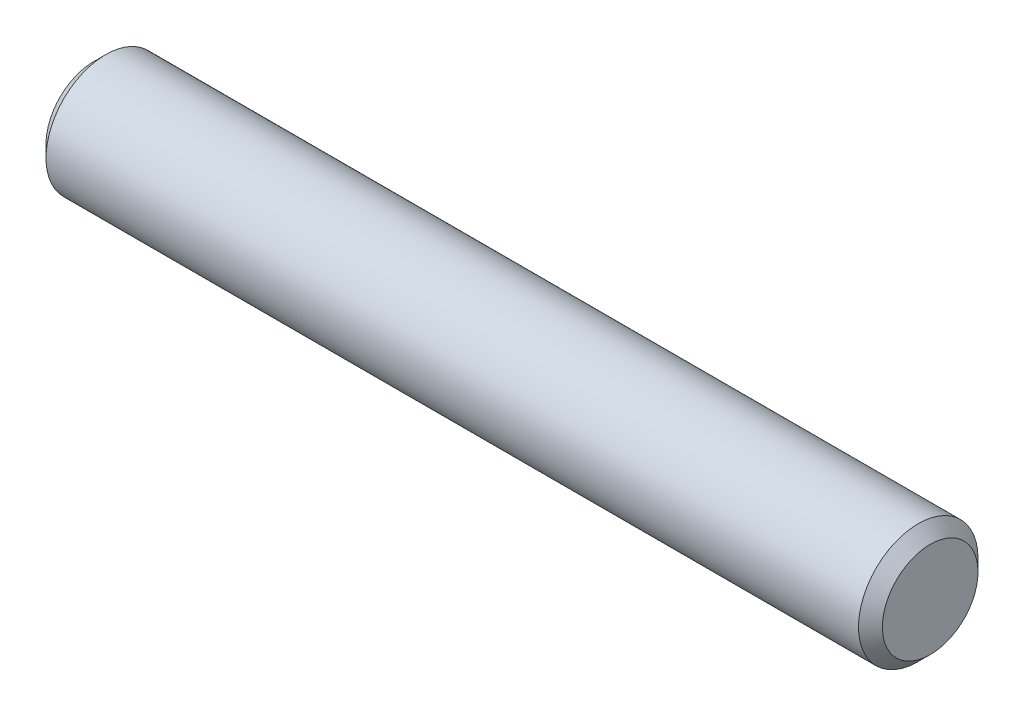
SolidWorks part; units mm, degrees
material "Cast Alloy Steel"
ref_plane "Front" through (0, 0, 0) normal (0, 0, 1) x (1, 0, 0)
ref_plane "Top" through (0, 0, 0) normal (0, 1, 0) x (1, 0, 0)
ref_plane "Right" through (0, 0, 0) normal (1, 0, 0) x (0, 0, -1)
sketch "Sketch1" plane through (0, 0, 0) normal (0, 0, 1) x (1, 0, 0)
  line L0 (-11.1125, 0) -> (11.1125, 0) construction
  line L1 (11.1125, 1.5875) -> (11.1125, -1.5875) construction
  line L2 (-11.1125, 1.5875) -> (-11.1125, -1.5875) construction
  dimension "Length" = 22.225
  dimension "Diameter" = 3.175
sketch "Sketch2" plane through (0, 0, 0) normal (1, 0, 0) x (0, 0, -1)
  circle A0 centre (0, 0) radius 1.5875
extrude "Extrude1" add sketch "Sketch2" against normal up to vertex (11.1125 mm away) and the other way up to vertex (11.1125 mm away) up to point (-11.1125, 1.5875, 0) other way up to point (11.1125, 1.5875, 0)
chamfer "Chamfer1" distance 0.3175 angle 45 2 edges at (11.1125, 0, -1.5875) (-11.1125, 0, -1.5875)
equation "\"D1@Chamfer1\" = \"Diameter@Sketch1\"*.1"
